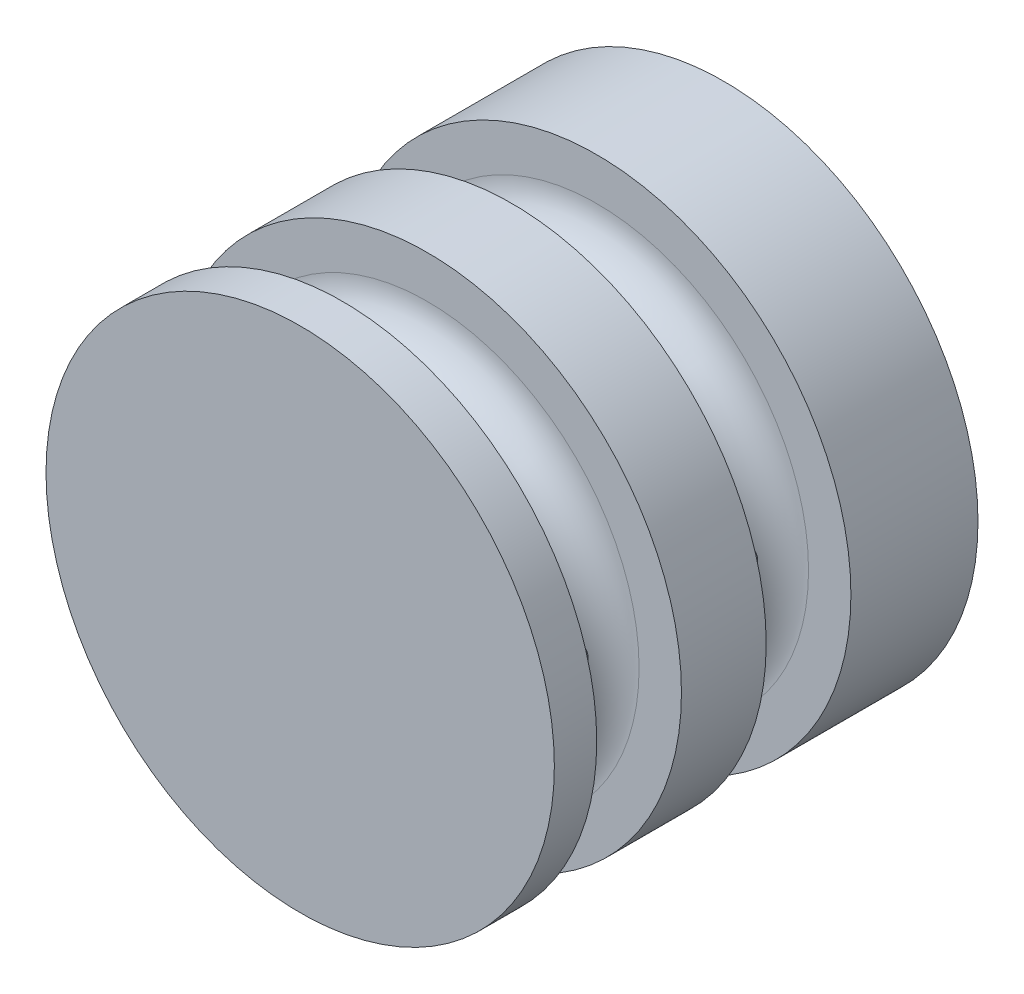
SolidWorks part; units mm, degrees
material "PLA"
ref_plane "Front Plane" through (0, 0, 0) normal (0, 0, 1) x (1, 0, 0)
ref_plane "Top Plane" through (0, 0, 0) normal (0, 1, 0) x (1, 0, 0)
ref_plane "Right Plane" through (0, 0, 0) normal (1, 0, 0) x (0, 0, -1)
sketch "Sketch1" plane through (0, 0, 0) normal (0, 0, 1) x (1, 0, 0)
  circle A0 centre (0, 0) radius 10
  circle A1 centre (0, 0) radius 15
  circle A2 centre (0, 0) radius 7 construction
  circle A3 centre (0, 0) radius 3.5
  point P5 (0, 7)
  point P6 (7, 0)
  point P7 (0, -7)
  point P8 (-7, 0)
  dimension "D1" = 20
  dimension "D2" = 5
  dimension "D3" = 14
  dimension "D4" = 7
sketch "Sketch2" plane through (0, 0, 0) normal (1, 0, 0) x (0, 0, -1)
  line L0 (0, 15) -> (20, 15)
  line L1 (0, 15) -> (0, -15)
  line L2 (20, 15) -> (20, -15)
  line L3 (0, -15) -> (20, -15)
  line L4 (17.5, 12.5) -> (17.5, 15)
  line L5 (12.5, 12.5) -> (12.5, 15)
  line L6 (17.5, -12.5) -> (17.5, -15)
  line L7 (0, 10) -> (20, 10) construction
  line L8 (0, -10) -> (20, -10) construction
  line L9 (12.5, -12.5) -> (12.5, -15)
  line L10 (7.5, -12.5) -> (7.5, -15)
  line L11 (2.5, -12.5) -> (2.5, -15)
  line L12 (10, 15) -> (10, -15) construction
  line L13 (20, -15) -> (20, 15)
  line L14 (0, 0) -> (10, 0)
  line L15 (10, 0) -> (20, 0)
  line L16 (2.5, 12.5) -> (2.5, 15)
  line L17 (7.5, 12.5) -> (7.5, 15)
  line L18 (20, -15) -> (25, -15)
  line L19 (20, 15) -> (25, 15)
  line L20 (25, -15) -> (25, 15)
  line L21 (20, 0) -> (25, 0)
  circle A0 centre (5, 0) radius 1.5
  circle A1 centre (15, 0) radius 1.5
  circle A2 centre (5, 12.5) radius 2.5
  circle A3 centre (15, 12.5) radius 2.5
  circle A4 centre (15, -12.5) radius 2.5
  circle A5 centre (5, -12.5) radius 2.5
  point P0 (0, 15)
  point P3 (0, -15)
  point P10 (0, 10)
  point P12 (0, -10)
  dimension "D4" = 3
  dimension "D1" = 5
  dimension "D2" = 10
revolve "Revolve5" add sketch "Sketch2" angle 360 about L14 region at (0, 6.7546, -10) region at (0, 0.6366, -5) region at (0, 0.6366, -15) region at (0, 7.5, -22.5)
extrude "Cut-Extrude1" cut sketch "Sketch2<6>" against normal through all both and the other way through all contours A0 | A1
sketch "Sketch2<6>" plane through (0, 0, 0) normal (1, 0, 0) x (0, 0, -1) same geometry as "Sketch2"
sketch "Sketch5" plane through (0, 0, -25) normal (0, 0, -1) x (-1, 0, 0)
  point P0 (0, 7)
  point P3 (7, 0)
  point P6 (0, -7)
  point P9 (-7, 0)
hole_wizard "M3 Clearance Hole1" positions "Sketch5" profile "Sketch6" hole size "M3" standard "ANSI Metric"
sketch "Sketch6" plane through (0, 7, -25) normal (1, 0, 0) x (0, 1, 0)
  line L0 (0, 0) -> (0, 5.9614)
  line L1 (0, 5.9614) -> (1.6, 5)
  line L2 (1.6, 5) -> (1.6, 0)
  line L5 (1.6, 0) -> (0, 0)
  line L10 (0, 5.9614) -> (-1.6, 5) construction
  line L11 (0, -6.35) -> (0, 107.95) construction
  dimension "Hole Dia." = 3.2
  dimension "Hole Depth" = 5
  dimension "Drill Angle" = 118
extrude "Cut-Extrude2" cut sketch "Sketch1" along normal blind 5 from surface contours A3 starting at face at (-1.6, 7, -25)
